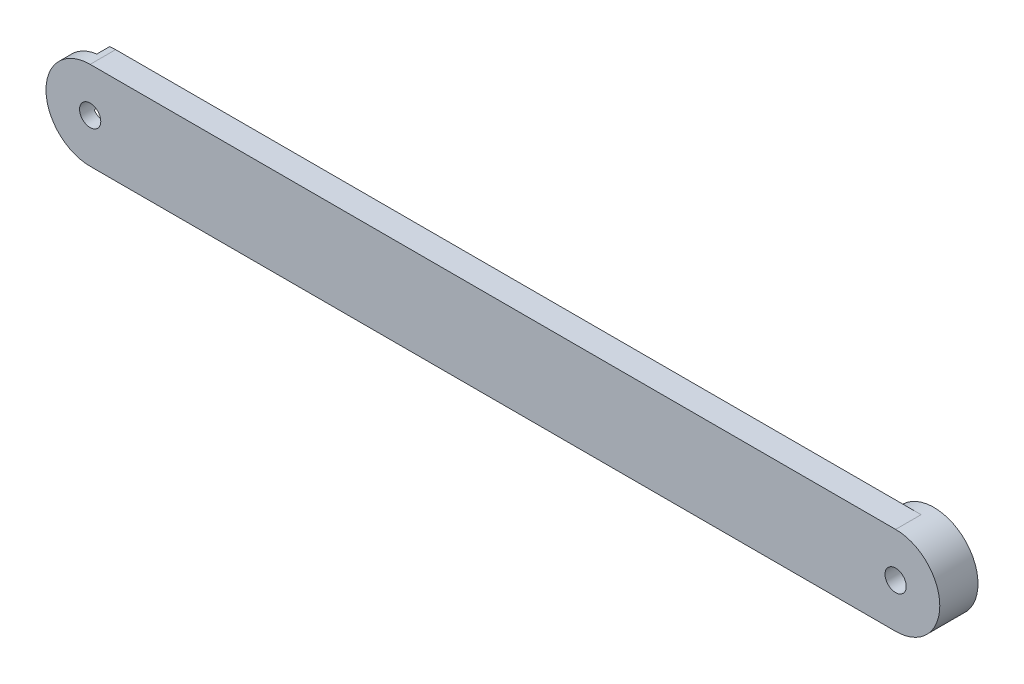
SolidWorks part; units mm, degrees
ref_plane "Front Plane" through (0, 0, 0) normal (0, 0, 1) x (1, 0, 0)
ref_plane "Top Plane" through (0, 0, 0) normal (0, 1, 0) x (1, 0, 0)
ref_plane "Right Plane" through (0, 0, 0) normal (1, 0, 0) x (0, 0, -1)
sketch "Sketch1" plane through (0, 0, 0) normal (0, 0, 1) x (1, 0, 0)
  line L0 (189.7, -10.4) -> (0, -10.4)
  line L1 (189.7, 10.4) -> (0, 10.4)
  circle A4 centre (0, 0) radius 2.5
  circle A5 centre (189.7, 0) radius 2.5
  arc A6 (0, 10.4) -> (0, -10.4) centre (0, 0) ccw
  arc A7 (189.7, -10.4) -> (189.7, 10.4) centre (189.7, 0) ccw
  arc A9 (0, -10.4) -> (0, 10.4) centre (0, 0) ccw construction
  circle A10 centre (0, 0) radius 10.4 construction
  arc A11 (189.7, 10.4) -> (189.7, -10.4) centre (189.7, 0) ccw construction
  circle A12 centre (189.7, 0) radius 10.4 construction
  circle A13 centre (189.7, 0) radius 1.4996 construction
  circle A15 centre (0, 0) radius 2.4001
  point P1 (0, 0)
  point P4 (0, 0)
  point P5 (0, 0)
  point P11 (170.2346, 97.4995)
  point P18 (75.4, 97.5)
  dimension "D1" = 5
  dimension "D3" = 1.0004
  dimension "D4" = 4.8001
  dimension "D2" = 10.4
  dimension "D5" = 189.7
extrude "Boss-Extrude1" add sketch "Sketch1" along normal blind 6 contours L0 A7 L1 A6 A4 A5 region at (94.85, 0, 0)
sketch "Sketch6" plane through (0, 0, 0) normal (0, 0, -1) x (-1, 0, 0)
  line L0 (0, 0) -> (6.6622, 8.2447) construction
  line L1 (0, 0) -> (-10.4, 0) construction
  line L2 (0, 0) -> (9.892, 3.8091) construction
  line L3 (0, 0) -> (1.6472, 10.4712) construction
  line L4 (2.3974, 0.7088) -> (9.9638, 3.6224)
  line L5 (0.1897, 2.4928) -> (1.4497, 10.5023)
  line L6 (-0.5848, -2.4306) -> (-1.8448, -10.4401)
  line L7 (0.0719, -0.1866) -> (9.9638, 3.6224) construction
  line L8 (-0.1976, 0.0311) -> (1.4497, 10.5023) construction
  line L9 (2.064, -1.4107) -> (8.3704, -6.5066)
  line L10 (0.1257, 0.1556) -> (8.3704, -6.5066) [skipped]
  line L11 (-0.1976, 0.0311) -> (-1.8448, -10.4401) [skipped]
  line L12 (0.0719, -0.1866) -> (-9.8201, -3.9957) [skipped]
  line L13 (0.1257, 0.1556) -> (-8.119, 6.8177) [skipped]
  line L14 (-1.8126, 1.7218) -> (-8.119, 6.8177)
  line L15 (-2.2537, -1.0821) -> (-9.8201, -3.9957)
  circle A0 centre (0, 0) radius 10.4 construction
  arc A1 (0, -10.4) -> (0, 10.4) centre (0, 0) ccw construction
  arc A2 (9.9621, 3.6217) -> (1.4494, 10.5004) centre (0, 0) ccw
  arc A3 (9.9621, 3.6217) -> (1.4494, 10.5004) centre (0, 0) ccw
  arc A4 (9.9621, 3.6217) -> (1.4494, 10.5004) centre (0, 0) ccw
  circle A5 centre (0, 0) radius 2.5 construction
  arc A6 (2.3974, 0.7088) -> (0.1897, 2.4928) centre (0, 0) ccw
  arc A7 (-0.5848, -2.4306) -> (2.064, -1.4107) centre (0, 0) ccw
  circle A8 centre (0, 0) radius 10.6 construction
  arc A9 (-1.8445, -10.4383) -> (8.369, -6.5054) centre (0, 0) ccw
  arc A10 (-1.8126, 1.7218) -> (-2.2537, -1.0821) centre (0, 0) ccw
  arc A11 (-8.1176, 6.8165) -> (-9.8183, -3.995) centre (0, 0) ccw
  point P8 (-0.7033, -1.0005)
  point P13 (7.6704, -5.9409)
  point P14 (0.0719, -0.1866)
  point P15 (9.124, 3.299)
  point P22 (10.1368, 3.0991)
  point P27 (0, 0)
  point P34 (0, 0)
  point P51 (0, 0)
  circle M6 centre (0, 0) radius 2.5
  line M8 (-189.7, -10.4) -> (0, -10.4)
  arc M9 (0, -10.4) -> (0, 10.4) centre (0, 0) ccw
  dimension "D3" = 60
  dimension "D2" = 128.94
  dimension "D4" = 30
  dimension "D6" = 0.2
  dimension "D8" = 3
  dimension "D1" = 0.2
  dimension "D5" = 0.2
  dimension "D7" = 3
extrude "Cut-Extrude3" cut sketch "Sketch6" against normal blind 3 contours L5 L4 M6 M9 | L9 L6 M6 M8 M9 | L14 A11 L15 M6 region at (-4.3061, 5.329, 0) region at (-2.4553, -6.4005, 0) region at (6.8883, 1.0836, 0)
sketch "Sketch4" plane through (0, 0, 0) normal (0, 0, -1) x (-1, 0, 0)
  arc A0 (-189.7, 10.4) -> (-189.7, -10.4) centre (-189.7, 0) ccw construction
  arc A1 (-189.7, 10.4) -> (-189.7, -10.4) centre (-189.7, 0) ccw
  arc A2 (-189.7, 10.4) -> (-189.7, -10.4) centre (-189.7, 0) cw
  circle A3 centre (-189.7, 0) radius 2.5 construction
  circle A4 centre (-189.7, 0) radius 2.5
extrude "Boss-Extrude2" add sketch "Sketch4" along normal blind 3
